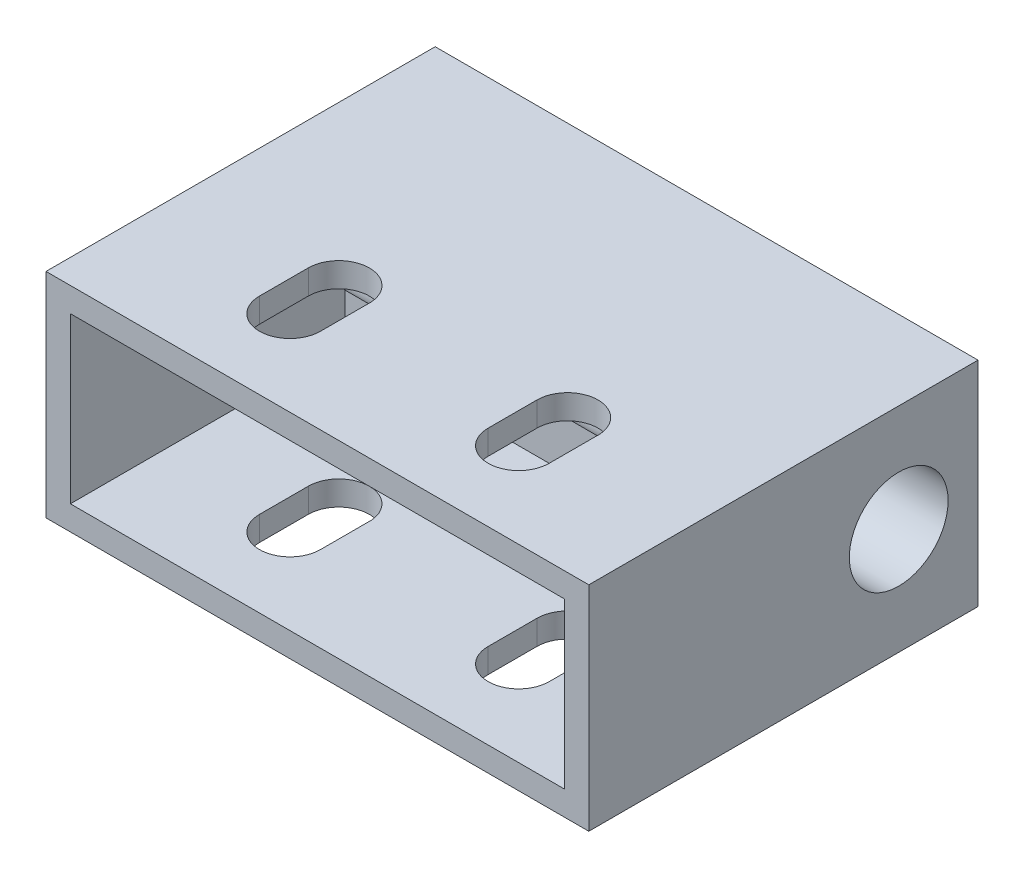
SolidWorks part; units mm, degrees
ref_plane "Front Plane" through (0, 0, 0) normal (0, 0, 1) x (1, 0, 0)
ref_plane "Top Plane" through (0, 0, 0) normal (0, 1, 0) x (1, 0, 0)
ref_plane "Right Plane" through (0, 0, 0) normal (1, 0, 0) x (0, 0, -1)
sketch "Sketch1" plane through (0, 0, 0) normal (0, 1, 0) x (1, 0, 0)
  line L1 (0, 0) -> (22.606, 0)
  line L2 (0, 0) -> (0, 16.2084)
  line L3 (0, 16.2084) -> (22.606, 16.2084)
  line L4 (22.606, 0) -> (22.606, 16.2084)
  dimension "D1" = 16.2084
  dimension "D2" = 22.606
extrude "Boss-Extrude1" add sketch "Sketch1" along normal blind 8.89
sketch "Sketch2" plane through (0, 0, 0) normal (0, 0, 1) x (1, 0, 0)
  line L0 (0, 8.89) -> (22.606, 8.89) construction
  line L1 (1.016, 7.874) -> (21.59, 7.874)
  line L2 (1.016, 7.874) -> (1.016, 1.016)
  line L3 (1.016, 1.016) -> (21.59, 1.016)
  line L4 (21.59, 7.874) -> (21.59, 1.016)
  line L5 (0, 8.89) -> (0, 0) construction
  dimension "D1" = 1.016
  dimension "D2" = 1.016
  dimension "D3" = 20.574
  dimension "D4" = 6.858
extrude "Cut-Extrude1" cut sketch "Sketch2" against normal blind 11.43
sketch "Sketch3" plane through (0, 8.89, 0) normal (0, 1, 0) x (1, 0, 0)
  line L0 (22.606, 0) -> (22.606, 16.2084) construction
  line L2 (0, 0) -> (22.606, 0) construction
  line L3 (5.334, 5.588) -> (7.874, 5.588)
  line L4 (5.334, 5.588) -> (5.334, 3.556)
  line L5 (5.334, 3.556) -> (7.874, 3.556)
  line L6 (7.874, 5.588) -> (7.874, 3.556)
  line L7 (14.859, 5.588) -> (17.399, 5.588)
  line L8 (14.859, 5.588) -> (14.859, 3.556)
  line L9 (14.859, 3.556) -> (17.399, 3.556)
  line L10 (17.399, 5.588) -> (17.399, 3.556)
  circle A0 centre (6.604, 3.556) radius 1.27
  circle A1 centre (16.129, 3.556) radius 1.27
  circle A2 centre (6.606, 5.588) radius 1.272
  circle A3 centre (16.131, 5.588) radius 1.272
  dimension "D1" = 9.525
  dimension "D2" = 6.477
  dimension "D3" = 3.556
  dimension "D4" = 2.032
  dimension "D5" = 2.032
sketch "Sketch5" plane through (22.606, 0, 0) normal (1, 0, 0) x (0, 0, -1)
  line L0 (0, 8.89) -> (16.2084, 8.89) construction
  line L1 (0, 8.89) -> (0, 0) construction
  circle A0 centre (12.9064, 4.445) radius 2.0574
  dimension "D1" = 4.445
  dimension "D2" = 12.9064
extrude "Cut-Extrude3" cut sketch "Sketch5" against normal blind 54.0265
extrude "Cut-Extrude4" cut sketch "Sketch3" against normal blind 22.7845 contours L5 A0 | A2 A0 L5 | A2 A0 L6 | A0 A2 | A2 L4 A0 | A0 A2 L3 | L3 A2 | A3 L8 A1 | A1 A3 | A1 A3 L7 | A3 A1 L9 | A3 A1 L10 | L9 A1 | L7 A3 region at (6.6061, 8.89, -6.1278) region at (5.4791, 8.89, -4.5718) region at (6.6061, 8.89, -5.174) region at (6.6037, 8.89, -3.9689) region at (6.604, 8.89, -3.017) region at (6.605, 8.89, -4.571) region at (7.7291, 8.89, -4.566) region at (16.1311, 8.89, -6.1278) region at (15.0041, 8.89, -4.5718) region at (16.1311, 8.89, -5.174) region at (16.1287, 8.89, -3.9689) region at (16.129, 8.89, -3.017) region at (16.13, 8.89, -4.571) region at (17.2541, 8.89, -4.566)
